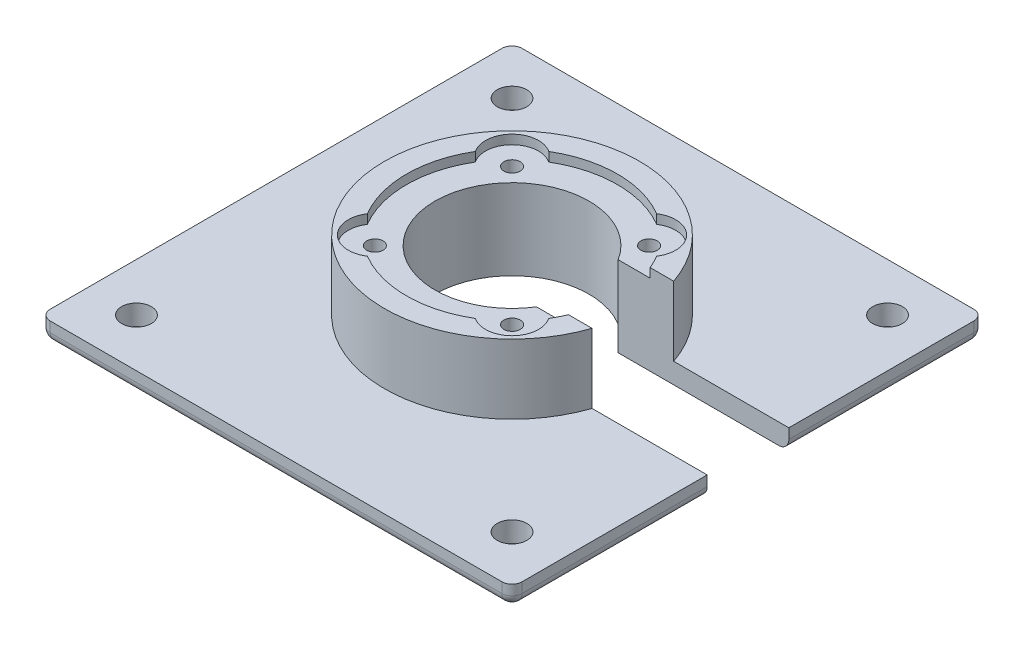
SolidWorks part; units mm, degrees
ref_plane "Front Plane" through (0, 0, 0) normal (0, 0, 1) x (1, 0, 0)
ref_plane "Top Plane" through (0, 0, 0) normal (0, 1, 0) x (1, 0, 0)
ref_plane "Right Plane" through (0, 0, 0) normal (1, 0, 0) x (0, 0, -1)
sketch "Sketch3" plane through (0, 0, 0) normal (0, 1, 0) x (1, 0, 0)
  circle A0 centre (0, 0) radius 7.55
  circle A1 centre (0, 0) radius 12.5
  dimension "D1" = 15.1
  dimension "D2" = 25
extrude "Boss-Extrude2" add sketch "Sketch3" along normal blind 8.8
sketch "Sketch4" plane through (0, 8.8, 0) normal (0, 1, 0) x (1, 0, 0)
  line L0 (6.4033, 4) -> (6.4033, -4)
  line L1 (6.4033, -4) -> (13.2817, -4)
  line L2 (13.2817, -4) -> (13.2817, 4)
  line L3 (13.2817, 4) -> (6.4033, 4)
  circle A0 centre (0, 0) radius 7.55 construction
  point P0 (0, 0)
  point P1 (6.4033, 4)
  point P3 (6.4033, -4)
  dimension "D1" = 4
extrude "Cut-Extrude2" cut sketch "Sketch4" against normal blind 8.8
sketch "Sketch5" plane through (0, 8.8, 0) normal (0, 1, 0) x (1, 0, 0)
  line L0 (0, 0) -> (17.4279, 0) construction
  line L1 (0, 0) -> (-11.2462, -11.2462) construction
  line L2 (0, 0) -> (-11.0539, 11.0539) construction
  point P0 (0, 0)
  point P1 (-6.715, 6.72)
  point P3 (-6.715, -6.72)
  point P9 (6.72, -6.715)
  point P10 (6.72, 6.715)
  dimension "D1" = 6.72
  dimension "D2" = 9.5
  dimension "D3" = 6.72
  dimension "D4" = 9.5
sketch "Sketch6" plane through (0, 8.8, 0) normal (0, 1, 0) x (1, 0, 0)
  line L0 (0, 0) -> (-11.2462, -11.2462) construction
  line L1 (0, 0) -> (-11.0539, 11.0539) construction
  line L2 (0, 0) -> (17.4279, 0) construction
  point P0 (5.2883, -8.8853)
  point P9 (-8.8853, 5.2883)
  point P12 (5.2883, 8.8853)
  point P14 (8.8893, -5.2817)
  point P15 (-5.2817, 8.8893)
  point P16 (8.8893, 5.2817)
  point P17 (-5.2817, -8.8893)
  point P18 (-8.8853, -5.2883)
  dimension "D1" = 2.6
  dimension "D2" = 10.34
  dimension "D3" = 2.6
  dimension "D4" = 10.34
sketch "Sketch8" plane through (0, 8.8, 0) normal (0, 1, 0) x (1, 0, 0)
  circle A0 centre (0, 0) radius 10.34
extrude "Cut-Extrude5" cut sketch "Sketch8" against normal blind 0.9
hole_wizard "Tap Drill for M2x0.4 Tap1" positions "3DSketch1" profile "Sketch10" hole size "M2x0.4" standard "ANSI Metric" end condition through all
sketch3d "3DSketch1"
  point P0 (6.72, 8.8, 6.715)
  point P3 (-6.715, 8.8, 6.72)
  point P6 (-6.715, 8.8, -6.72)
  point P9 (6.72, 8.8, -6.715)
sketch "Sketch10" plane through (6.72, 8.8, 6.715) normal (1, 0, 0) x (0, 0, 1)
  line L0 (0, 0) -> (0, 8.8)
  line L1 (0, 8.8) -> (0.8, 8.8)
  line L2 (0.8, 8.8) -> (0.8, 0)
  line L5 (0.8, 0) -> (0, 0)
  line L11 (0, -6.35) -> (0, 107.95) construction
  dimension "Thru Hole Dia." = 1.6
  dimension "Thru Hole Depth" = 8.8
sketch "Sketch11" plane through (0, 8.8, 0) normal (0, 1, 0) x (1, 0, 0)
  line L0 (8.8893, 5.2817) -> (5.2883, 8.8853)
  line L1 (8.8893, -5.2817) -> (5.2883, -8.8853)
  line L2 (-5.2817, -8.8893) -> (-8.8853, -5.2883)
  line L3 (-5.2817, 8.8893) -> (-8.8853, 5.2883)
  arc A0 (5.2883, -8.8853) -> (8.8893, -5.2817) centre (6.72, -6.715) ccw
  arc A1 (9.535, 4) -> (9.535, -4) centre (0, 0) ccw construction
  arc A2 (8.8893, 5.2817) -> (5.2883, 8.8853) centre (6.72, 6.715) ccw
  arc A3 (-5.2817, 8.8893) -> (-8.8853, 5.2883) centre (-6.715, 6.72) ccw
  arc A4 (-8.8853, -5.2883) -> (-5.2817, -8.8893) centre (-6.715, -6.72) ccw
extrude "Cut-Extrude6" cut sketch "Sketch11" against normal blind 0.9
sketch "Sketch12" plane through (0, 0, 0) normal (0, -1, 0) x (1, 0, 0)
  line L0 (0, 0) -> (17.7684, 0) construction
  line L1 (0, 0) -> (0, 18.0241) construction
  line L2 (23.125, -23.125) -> (-23.125, -23.125)
  line L3 (-23.125, -23.125) -> (-23.125, 23.125)
  line L4 (-23.125, 23.125) -> (23.125, 23.125)
  line L9 (6.4033, 4) -> (23.125, 4)
  line L11 (23.125, -4) -> (6.4033, -4)
  line L13 (23.125, -23.125) -> (23.125, -4)
  line L14 (23.125, 23.125) -> (23.125, 4)
  arc A0 (6.4033, -4) -> (6.4033, 4) centre (0, 0) cw
  arc A1 (6.4033, 4) -> (6.4033, -4) centre (0, 0) ccw construction
  point P0 (23.125, -23.125)
  point P4 (23.125, 23.125)
  point P5 (-23.125, 23.125)
  point P7 (-23.125, -23.125)
  dimension "D1" = 23.125
  dimension "D2" = 23.125
extrude "Boss-Extrude4" add sketch "Sketch12" against normal blind 2
fillet "Fillet2" radius 1 2 edges at (-23.125, 0, 0) (0, 0, 23.125)
fillet "Fillet3" radius 1 2 edges at (-22.8321, 0.2929, 22.8321) (-23.125, 1.5, 23.125)
sketch "Sketch13" plane through (0, 0, 0) normal (0, -1, 0) x (1, 0, 0)
  line L0 (0, 0) -> (-25.0462, 0) construction
  line L1 (0, 0) -> (0, 26.5218) construction
  point P0 (18.3989, -18.3989)
  point P5 (18.3989, 18.3989)
  point P6 (-18.3989, -18.3989)
  point P7 (-18.3989, 18.3989)
  dimension "D1" = 18.3989
  dimension "D2" = 18.3989
hole_wizard "M2.5 Clearance Hole1" positions "3DSketch2" profile "Sketch14" hole size "M2.5" standard "ANSI Metric" end condition through all
sketch3d "3DSketch2"
  point P0 (18.3989, 0, 18.3989)
  point P3 (18.3989, 0, -18.3989)
  point P6 (-18.3989, 0, -18.3989)
  point P9 (-18.3989, 0, 18.3989)
sketch "Sketch14" plane through (18.3989, 0, 18.3989) normal (1, 0, 0) x (0, 0, -1)
  line L0 (0, 0) -> (0, 8.8)
  line L1 (0, 8.8) -> (1.45, 8.8)
  line L2 (1.45, 8.8) -> (1.45, 0)
  line L5 (1.45, 0) -> (0, 0)
  line L11 (0, -6.35) -> (0, 107.95) construction
  dimension "Thru Hole Dia." = 2.9
  dimension "Thru Hole Depth" = 8.8
fillet "Fillet4" radius 1 7 edges at (23.125, 1.5, 23.125) (23.125, 0.2929, 22.8321) (-23.125, 1.5, -23.125) (-22.8321, 0.2929, -23.125) (23.125, 0, 13.0625) (23.125, 0, -13.5625) (0.5, 0, -23.125)
fillet "Fillet5" radius 1 2 edges at (22.8321, 0.2929, -22.8321) (23.125, 1.5, -23.125)
